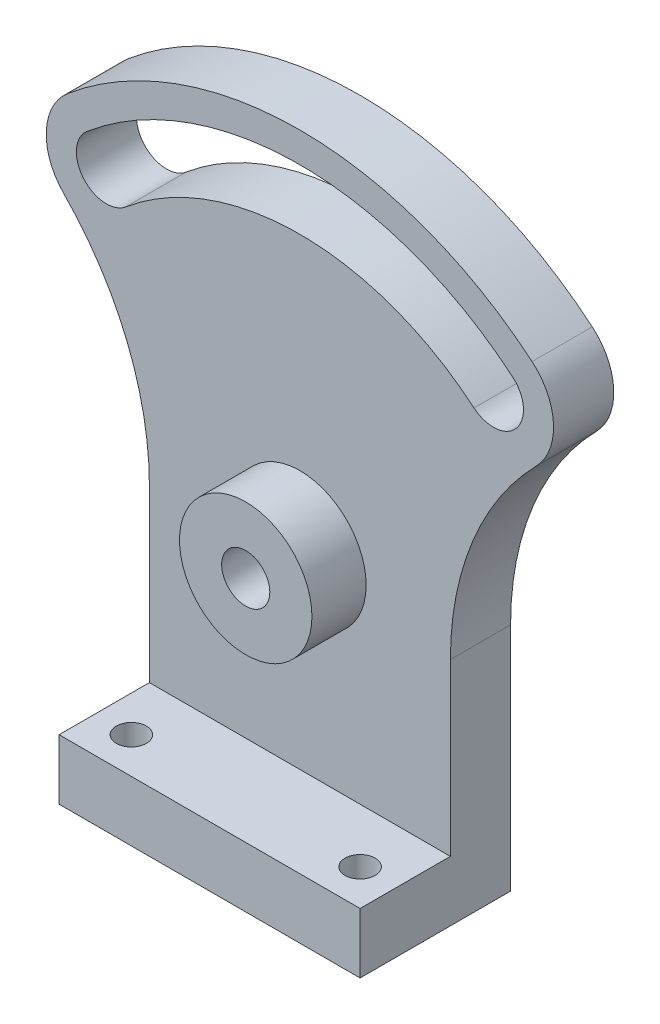
SolidWorks part; units mm, degrees
ref_plane "Front Plane" through (0, 0, 0) normal (0, 0, 1) x (1, 0, 0)
ref_plane "Top Plane" through (0, 0, 0) normal (0, 1, 0) x (1, 0, 0)
ref_plane "Right Plane" through (0, 0, 0) normal (1, 0, 0) x (0, 0, -1)
sketch "Sketch1" plane through (0, 0, 0) normal (0, 0, 1) x (1, 0, 0)
  line L0 (0, 0) -> (0, -35777.5834) construction
  line L1 (0, 0) -> (-35777.5834, 0) construction
  line L2 (-25, 10) -> (25, 10)
  line L4 (-25, 38.3145) -> (-25, 0)
  line L5 (-25, 0) -> (25, 0)
  line L6 (25, 38.3145) -> (25, 0)
  circle A0 centre (0, 42) radius 4
  circle A1 centre (0, 42) radius 11
  arc A2 (-32.1394, 80.3022) -> (32.1394, 80.3022) centre (0, 42) cw construction
  arc A3 (35.3533, 84.1324) -> (-35.3533, 84.1324) centre (0, 42) ccw
  arc A4 (28.9254, 76.472) -> (-28.9254, 76.472) centre (0, 42) ccw
  arc A5 (28.9254, 76.472) -> (35.3533, 84.1324) centre (32.1394, 80.3022) ccw
  arc A6 (-35.3533, 84.1324) -> (-28.9254, 76.472) centre (-32.1394, 80.3022) ccw
  arc A7 (32.1394, 80.3022) -> (-32.1394, 80.3022) centre (0, 42) ccw construction
  arc A8 (38.5673, 87.9627) -> (-38.5673, 87.9627) centre (0, 42) ccw
  arc A9 (25.7115, 72.6418) -> (-25.7115, 72.6418) centre (0, 42) ccw
  arc A10 (25.7115, 72.6418) -> (38.5673, 87.9627) centre (32.1394, 80.3022) ccw
  arc A11 (-38.5673, 87.9627) -> (-25.7115, 72.6418) centre (-32.1394, 80.3022) ccw
  arc A12 (25, 38.3145) -> (39.2828, 73.3043) centre (75, 38.3145) cw
  arc A13 (-25, 38.3145) -> (-39.2828, 73.3043) centre (-75, 38.3145) ccw
  point P16 (0, 92)
  point P21 (0, 92)
  dimension "D4" = 8
  dimension "D5" = 22
  dimension "D6" = 50
  dimension "D8" = 10
  dimension "D9" = 5
  dimension "D10" = 80
  dimension "D12" = 50
  dimension "D1" = 50
  dimension "D3" = 10
  dimension "D7" = 64.2788
  dimension "D11" = 42
extrude "Boss-Extrude1" add sketch "Sketch1" along normal blind 25 contours L6 L2 L4 L5 region at (0, 5, 0)
extrude "Boss-Extrude2" add sketch "Sketch1<3>" along normal blind 10 contours A0 | A13 L4 L2 L6 A12 A10 A9 A11 A1 | A8 A11 A9 A10 A6 A3 A5 A4 region at (-23.9343, 24.1573, 0) region at (0, 86.0847, 0) region at (0, 42, 0)
sketch "Sketch1<3>" plane through (0, 0, 0) normal (0, 0, 1) x (1, 0, 0) same geometry as "Sketch1"
extrude "Boss-Extrude4" add sketch "Sketch1<5>" along normal blind 19 contours A1 A0 region at (-10.6889, 42, 0)
sketch "Sketch1<5>" plane through (0, 0, 0) normal (0, 0, 1) x (1, 0, 0) same geometry as "Sketch1"
hole_wizard "Ø5.0mm Dowel Hole2" positions "Sketch11" profile "Sketch12" hole size "Ø5.0" standard "AS" end condition up to next
sketch "Sketch11" plane through (0, 10, 0) normal (0, 1, 0) x (1, 0, 0)
  line L0 (-25, -25) -> (-25, -10) construction
  line L1 (-25, -25) -> (25, -25) construction
  line L2 (25, -25) -> (25, -10) construction
  point P0 (-19, -19)
  point P2 (19, -19)
  point P9 (-70.4389, -12.6375)
  dimension "D1" = 6
  dimension "D2" = 6
  dimension "D3" = 6
  dimension "D4" = 6
sketch "Sketch12" plane through (-19, 10, 19) normal (1, 0, 0) x (0, 0, 1)
  line L0 (0, 0) -> (0, 10)
  line L1 (0, 10) -> (2.5, 10)
  line L2 (2.5, 10) -> (2.5, 0)
  line L5 (2.5, 0) -> (0, 0)
  line L11 (0, -6.35) -> (0, 107.95) construction
  dimension "Thru Hole Dia." = 5
  dimension "Thru Hole Depth" = 10
